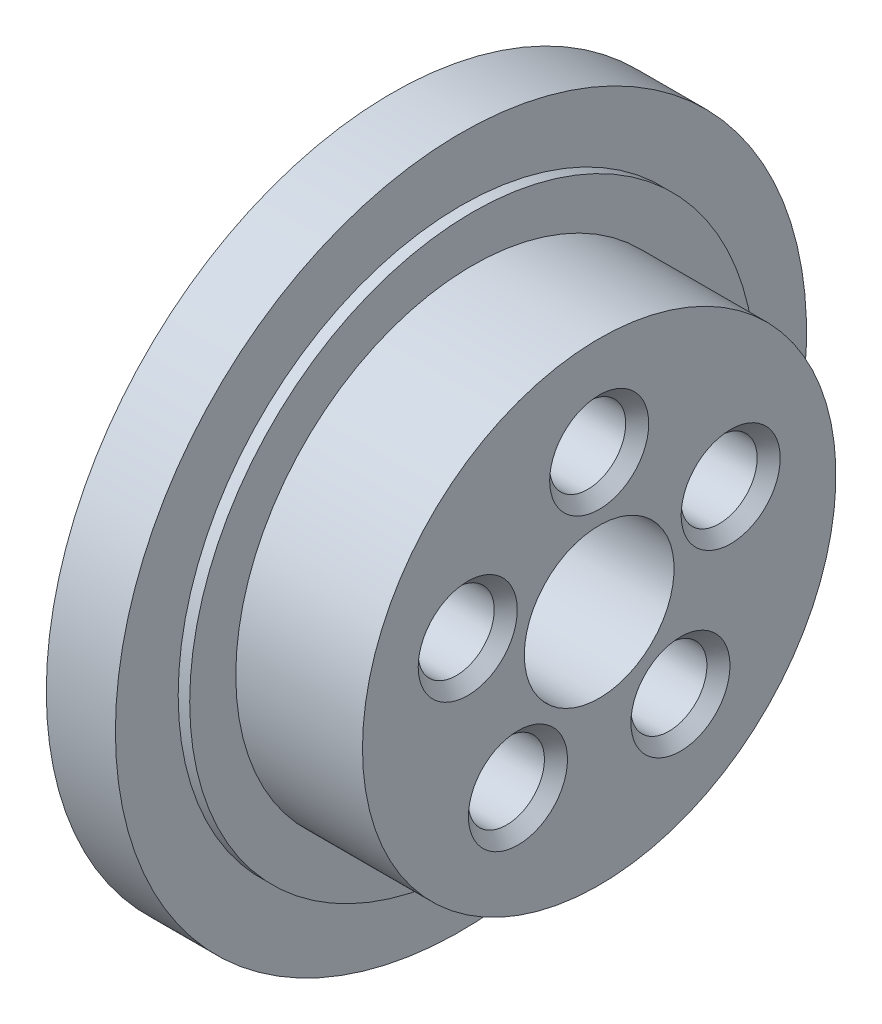
SolidWorks part; units mm, degrees
ref_plane "Front Plane" through (0, 0, 0) normal (0, 0, 1) x (1, 0, 0)
ref_plane "Top Plane" through (0, 0, 0) normal (0, 1, 0) x (1, 0, 0)
ref_plane "Right Plane" through (0, 0, 0) normal (1, 0, 0) x (0, 0, -1)
sketch "Sketch1" plane through (0, 0, 0) normal (0, 0, 1) x (1, 0, 0)
  line L0 (0, 30) -> (6, 30)
  line L9 (6, 30) -> (6, 24.55)
  line L10 (6, 24.55) -> (7, 24.55)
  line L11 (7, 24.55) -> (7, 20.55)
  line L12 (7, 20.55) -> (18, 20.55)
  line L13 (18, 20.55) -> (18, 6.5)
  line L14 (18, 6.5) -> (6, 6.5)
  line L15 (6, 6.5) -> (6, 7.5)
  line L16 (6, 7.5) -> (0, 7.5)
  line L17 (0, 7.5) -> (0, 30)
  line L18 (0, 0) -> (18, 0) construction
  dimension "D1" = 6
  dimension "D2" = 12
  dimension "D3" = 1
  dimension "D4" = 6
  dimension "D5" = 4
  dimension "D6" = 7.5
  dimension "D7" = 30
  dimension "D8" = 14.05
  dimension "D9" = 6.5
revolve "Revolve1" add sketch "Sketch1" angle 360 about L18
sketch "Sketch2" plane through (0, 0, 0) normal (-1, 0, 0) x (0, 0, 1)
  circle A0 centre (0, 0) radius 20 construction
  circle A1 centre (0, 20) radius 2.5
  circle A2 centre (17.3205, 10) radius 2.5
  circle A3 centre (17.3205, -10) radius 2.5
  circle A4 centre (0, -20) radius 2.5
  circle A5 centre (-17.3205, -10) radius 2.5
  circle A6 centre (-17.3205, 10) radius 2.5
  point P18 (0, 0)
  dimension "D1" = 40
  dimension "D2" = 5
extrude "Cut-Extrude1" cut sketch "Sketch2" against normal blind 4.5
sketch "Sketch3" plane through (18, 0, 0) normal (1, 0, 0) x (0, 0, -1)
  circle A0 centre (0, 0) radius 12 construction
  circle A3 centre (0, 12) radius 3.3
  circle A6 centre (11.4127, 3.7082) radius 3.3
  circle A7 centre (7.0534, -9.7082) radius 3.3
  circle A8 centre (-7.0534, -9.7082) radius 3.3
  circle A9 centre (-11.4127, 3.7082) radius 3.3
  point P15 (0, 0)
  dimension "D1" = 24
  dimension "D2" = 6.6
extrude "Cut-Extrude2" cut sketch "Sketch3" against normal blind 10.5
chamfer "Chamfer1" distance 1 angle 45 5 edges at (18, 3.7082, 8.1127) (18, -9.7082, 3.7534) (18, -9.7082, -10.3534) (18, 3.7082, -14.7127) (18, 12, -3.3)
equation "\"R_ROLL\"= 5mm"
equation "\"D_SUN\"= 80mm"
equation "\"NUM_ROLL\"= 16"
equation "\"RHO\"= 1mm"
equation "\"D_SHAFT\"= 15mm"
equation "\"D_OUTPUT\"= 40mm"
equation "\"NUM_OUT\"= 6"
equation "\"R_OUT_ROLL\"= 5mm"
equation "\"D1@Sketch2\"=\"D_OUTPUT\""
